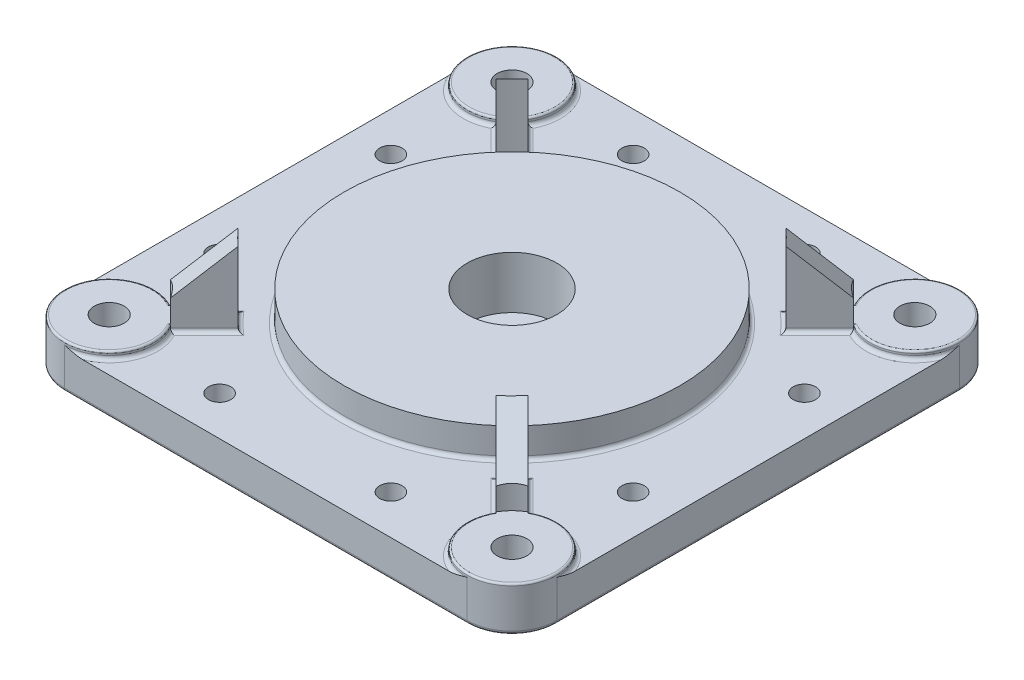
SolidWorks part; units mm, degrees
ref_plane "Front Plane" through (0, 0, 0) normal (0, 0, 1) x (1, 0, 0)
ref_plane "Top Plane" through (0, 0, 0) normal (0, 1, 0) x (1, 0, 0)
ref_plane "Right Plane" through (0, 0, 0) normal (1, 0, 0) x (0, 0, -1)
sketch "Sketch1" plane through (0, 0, 0) normal (0, 1, 0) x (1, 0, 0)
  line L1 (-27, -33) -> (27, -33)
  line L2 (-33, -27) -> (-33, 27)
  line L3 (-27, 33) -> (27, 33)
  line L4 (33, -27) -> (33, 27)
  line L5 (-31.2426, -31.2426) -> (31.2426, 31.2426) construction
  line L6 (-31.2426, 31.2426) -> (31.2426, -31.2426) construction
  circle A0 centre (27, 27) radius 6
  circle A1 centre (27, 27) radius 2
  circle A2 centre (27, -27) radius 6
  circle A3 centre (27, -27) radius 2
  circle A4 centre (-27, -27) radius 6
  circle A5 centre (-27, -27) radius 2
  circle A6 centre (-27, 27) radius 6
  circle A7 centre (-27, 27) radius 2
  circle A8 centre (0, 0) radius 22.5
  point P0 (0, 0)
  point P21 (0, 0)
  dimension "D3" = 12
  dimension "D4" = 6
  dimension "D5" = 4
  dimension "D6" = 4
  dimension "D7" = 27
  dimension "D1" = 45
extrude "Boss-Extrude1" add sketch "Sketch1" along normal blind 5 contours A6 L2 A4 L1 A2 L4 A0 L3 A8 region at (-22.0974, 0, 31.9026)
extrude "Boss-Extrude2" add sketch "Sketch1<3>" along normal blind 6 contours A4 A5 | A6 A7 | A0 A1 | A2 A3 region at (-31.1226, 0, 31.1226) region at (22.8774, 0, 22.8774) region at (-31.1226, 0, -31.1226) region at (22.8774, 0, -22.8774)
sketch "Sketch1<3>" plane through (0, 0, 0) normal (0, 1, 0) x (1, 0, 0) same geometry as "Sketch1"
extrude "Boss-Extrude3" add sketch "Sketch1<4>" along normal blind 9 contours A8 region at (0, 0, 0)
sketch "Sketch1<4>" plane through (0, 0, 0) normal (0, 1, 0) x (1, 0, 0) same geometry as "Sketch1"
sketch "Sketch2" plane through (0, 5, 0) normal (0, 1, 0) x (1, 0, 0)
  line L0 (19.4148, 17.2935) -> (23.9527, 21.8314)
  line L1 (17.2935, 19.4148) -> (21.8314, 23.9527)
  line L2 (0, 0) -> (36.6123, 36.6123) construction
  line L3 (0, 40.0187) -> (0, -39.2936) construction
  circle A0 centre (0, 0) radius 26 construction
  circle A1 centre (0, 0) radius 30 construction
  circle A2 centre (27, 27) radius 6 construction
  arc A3 (27, 33) -> (33, 27) centre (27, 27) ccw construction
  arc A4 (19.4148, 17.2935) -> (17.2574, 19.4469) centre (0, 0) ccw
  arc A5 (23.9527, 21.8314) -> (21.8314, 23.9527) centre (27, 27) cw
  circle A6 centre (-11.4805, 27.7164) radius 1.6327
  point P14 (22.7574, 22.7574)
  point P20 (0, 0)
  point P23 (0, 30)
  arc M13 (33, 27) -> (27, 33) centre (27, 27) cw
  dimension "D1" = 52
  dimension "D2" = 60
  dimension "D3" = 3
  dimension "D4" = 3
  dimension "D5" = 1.5
  dimension "D6" = 45
  dimension "D7" = 22.5
extrude "Boss-Extrude4" add sketch "Sketch2" along normal blind 10 contours A4 L0 L1 M13 region at (20.5884, 5, -20.5884)
sketch "Sketch3" plane through (1.0607, 0, 1.0607) normal (0.7071, 0, 0.7071) x (0.7071, 0, -0.7071)
  line L0 (32.3743, 9) -> (25.9567, 15)
  line L1 (32.3743, 15) -> (32.3743, 6) construction
  line L2 (25.9567, 15) -> (25.9567, 5) construction
  line L3 (25.9567, 5) -> (32.3743, 5) construction
  line L4 (25.9567, 15) -> (32.3743, 15) construction
  line L5 (32.3743, 9) -> (32.3743, 15)
  line L6 (32.3743, 15) -> (25.9567, 15)
  dimension "D1" = 4
extrude "Cut-Extrude1" cut sketch "Sketch3" against normal blind 10
pattern_circular "CirPattern1" count 4 over 360 about axis through (0, 15, 0) along (0, -1, 0) of "Cut-Extrude1", "Boss-Extrude4"
sketch "Sketch6" plane through (0, 0, 0) normal (0, -1, 0) x (-1, 0, 0)
  point P0 (11.4805, 27.7164)
hole_wizard "Hole1" positions "Sketch6" profile "Sketch7" legacy
sketch "Sketch7" plane through (-11.4805, 0, -27.7164) normal (1, 0, 0) x (0, 0, -1)
  line L0 (0, 0) -> (0, 100)
  line L1 (0, 100) -> (1.5, 100)
  line L2 (1.5, 100) -> (1.5, 0.5)
  line L3 (1.5, 0.5) -> (2, 0)
  line L4 (2, 0) -> (0, 0)
  line L5 (0, -6.4453) -> (0, 115.525) construction
  line L6 (-1.5, 0.5) -> (-2, 0) construction
  dimension "Diameter" = 3
  dimension "Depth" = 100
  dimension "C-Sink Angle" = 90
  dimension "C-Sink Diameter" = 4
pattern_circular "CirPattern2" count 8 over 360 about axis through (0, 9, 0) along (0, -1, 0) of "Hole1"
sketch "Sketch8" plane through (0, 9, 0) normal (0, 1, 0) x (1, 0, 0)
  circle A0 centre (0, 0) radius 6
  dimension "D1" = 12
extrude "Cut-Extrude2" cut sketch "Sketch8" against normal blind 7
fillet "Fillet1" radius 0.5 41 edges at (-27.7164, 0, -13.4805) (27.7164, 0, -13.4805) (11.4805, 0, -29.7164) (27, 0, 29) (27, 0, -25) (-27, 0, -25) (-27, 0, 29) (-31.2426, 0, 31.2426) (0, 0, 33) (31.2426, 0, 31.2426) (33, 0, 0) (31.2426, 0, -31.2426) (0, 0, -33) (-31.2426, 0, -31.2426) (-33, 0, 0) (-11.4805, 0, -29.7164) (27.7164, 0, 9.4805) (11.4805, 0, 25.7164) (-11.4805, 0, 25.7164) (-27.7164, 0, 9.4805) (0, 5, 22.5) (21.7902, 5, -29.9763) (19.5625, 5, -21.6838) (18.3848, 5, -18.3848) (21.6838, 5, -19.5625) (29.9763, 5, -21.7902) (18.3848, 5, 18.3848) (21.7902, 5, 29.9763) (19.5625, 5, 21.6838) (29.9763, 5, 21.7902) (21.6838, 5, 19.5625) (-29.9763, 5, -21.7902) (-21.6838, 5, -19.5625) (-21.7902, 5, -29.9763) (-18.3848, 5, -18.3848) (-19.5625, 5, -21.6838) (-29.9763, 5, 21.7902) (-21.6838, 5, 19.5625) (-18.3848, 5, 18.3848) (-19.5625, 5, 21.6838) (-21.7902, 5, 29.9763)
fillet "Fillet2" radius 0.25 4 edges at (-31.2426, 6, -31.2426) (31.2426, 6, -31.2426) (31.2426, 6, 31.2426) (-31.2426, 6, 31.2426)
